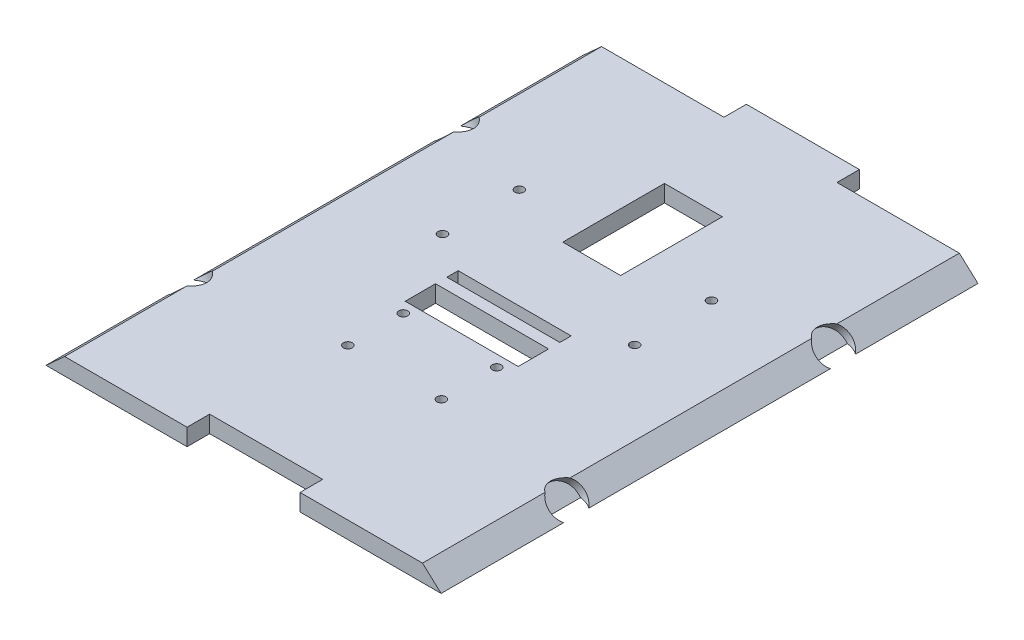
SolidWorks part; units mm, degrees
ref_plane "Front Plane" through (0, 0, 0) normal (0, 0, 1) x (1, 0, 0)
ref_plane "Top Plane" through (0, 0, 0) normal (0, 1, 0) x (1, 0, 0)
ref_plane "Right Plane" through (0, 0, 0) normal (1, 0, 0) x (0, 0, -1)
sketch "Sketch1" plane through (0, 0, 0) normal (0, 0, 1) x (1, 0, 0)
  line L0 (0, 0) -> (0, 44.45) construction
  line L1 (-40.2039, 5.9378) -> (40.2039, 5.9378)
  line L2 (-44.399, 2.1278) -> (44.399, 2.1278)
  line L3 (-40.2039, 5.9378) -> (-44.399, 2.1278)
  line L4 (40.2039, 5.9378) -> (44.399, 2.1278)
  arc A0 (44.399, 2.1278) -> (-44.399, 2.1278) centre (0, 0) ccw construction
  arc A1 (40.2039, 5.9378) -> (-40.2039, 5.9378) centre (0, 0) ccw construction
  dimension "D1" = 88.9
  dimension "D2" = 3.81
  dimension "D3" = 3.81
extrude "Boss-Extrude1" add sketch "Sketch1" along normal blind 120.65
sketch "Sketch3" plane through (0, 2.1278, 0) normal (0, -1, 0) x (1, 0, 0)
  line L0 (0, 120.65) -> (0, 0) construction
  line L1 (-44.399, 120.65) -> (44.399, 120.65) construction
  line L2 (-44.399, 0) -> (44.399, 0) construction
  line L3 (0, 60.325) -> (44.399, 60.325) construction
  line L4 (-12.7, 120.65) -> (12.7, 120.65)
  line L5 (-12.7, 120.65) -> (-12.7, 115.57)
  line L6 (-12.7, 115.57) -> (12.7, 115.57)
  line L7 (12.7, 120.65) -> (12.7, 115.57)
  line L8 (44.399, 120.65) -> (44.399, 0) construction
  line L9 (0, 60.325) -> (-44.399, 60.325) construction
  line L10 (-44.399, 120.65) -> (-44.399, 0) construction
  line L11 (12.7, -5.08) -> (12.7, 0) construction
  line L13 (-12.7, 0) -> (12.7, 0) construction
  line L14 (-12.7, -5.08) -> (-12.7, 0) construction
  line L15 (-12.7, -5.08) -> (12.7, -5.08) construction
  point P10 (12.7, 118.11)
  dimension "D1" = 25.4
  dimension "D2" = 12.7
  dimension "D3" = 5.08
extrude "Cut-Extrude1" cut sketch "Sketch3" against normal through all
sketch "Sketch4" plane through (0, 2.1278, 0) normal (0, -1, 0) x (1, 0, 0)
  line L0 (12.7, -5.0447) -> (12.7, 0.0353)
  line L1 (-12.7, 0.0353) -> (12.7, 0.0353)
  line L2 (-12.7, -5.0447) -> (-12.7, 0.0353)
  line L3 (-12.7, -5.0447) -> (12.7, -5.0447)
  line L4 (0, 115.57) -> (0, 0.0353) construction
  line L5 (-12.7, 115.57) -> (12.7, 115.57) construction
  dimension "D1" = 25.4
  dimension "D2" = 12.7
  dimension "D3" = 5.08
extrude "Boss-Extrude3" add sketch "Sketch4" against normal blind 3.81
sketch "Sketch5" plane through (0, 2.1278, 0) normal (0, -1, 0) x (-1, 0, 0)
  line L0 (0, -115.57) -> (0, 5.0447) construction
  line L1 (12.7, -115.57) -> (-12.7, -115.57) construction
  line L2 (12.7, 5.0447) -> (-12.7, 5.0447) construction
  line L3 (0, -88.6813) -> (0, -64.8053) construction
  line L4 (12.446, -88.6813) -> (-12.446, -88.6813) construction
  line L5 (12.446, -88.6813) -> (12.446, -64.8053) construction
  line L6 (12.446, -64.8053) -> (-12.446, -64.8053) construction
  line L7 (-12.446, -88.6813) -> (-12.446, -64.8053) construction
  line L8 (23.114, -55.88) -> (-23.114, -55.88) construction
  line L9 (23.114, -55.88) -> (23.114, -35.56) construction
  line L10 (23.114, -35.56) -> (-23.114, -35.56) construction
  line L11 (-23.114, -55.88) -> (-23.114, -35.56) construction
  line L12 (0, -55.88) -> (0, -35.56) construction
  line L13 (-23.114, -45.72) -> (23.114, -45.72) construction
  line L14 (12.446, -76.7433) -> (-12.446, -76.7433) construction
  line L15 (-95.9311, -70.6497) -> (-70.9311, -70.6497) construction
  line L16 (-95.9311, -70.6497) -> (-95.9311, -94.6497) construction
  line L17 (-95.9311, -94.6497) -> (-70.9311, -94.6497) construction
  line L18 (-70.9311, -70.6497) -> (-70.9311, -94.6497) construction
  line L19 (-73.5448, 8.1415) -> (-73.5448, -11.8585) construction
  line L20 (-96.4048, 8.1415) -> (-50.6848, 8.1415) construction
  line L21 (-96.4048, 8.1415) -> (-96.4048, -11.8585) construction
  line L22 (-96.4048, -11.8585) -> (-50.6848, -11.8585) construction
  line L23 (-50.6848, 8.1415) -> (-50.6848, -11.8585) construction
  line L24 (-96.4048, -1.8585) -> (-50.6848, -1.8585) construction
  line L25 (0, -19.558) -> (0, -42.418) construction
  line L26 (6.5, -19.558) -> (-6.5, -19.558)
  line L27 (6.5, -19.558) -> (6.5, -42.418)
  line L28 (6.5, -42.418) -> (-6.5, -42.418)
  line L29 (-6.5, -19.558) -> (-6.5, -42.418)
  line L30 (-12.7, 0) -> (-44.399, 0) construction
  line L31 (0, -62.2653) -> (0, -59.7253) construction
  line L32 (12.7, -62.2653) -> (-12.7, -62.2653)
  line L33 (12.7, -62.2653) -> (12.7, -59.7253)
  line L34 (12.7, -59.7253) -> (-12.7, -59.7253)
  line L35 (-12.7, -62.2653) -> (-12.7, -59.7253)
  line L36 (0, -71.6278) -> (0, -64.8053) construction
  line L37 (12.7, -71.6278) -> (-12.7, -71.6278)
  line L38 (12.7, -71.6278) -> (12.7, -64.8053)
  line L39 (12.7, -64.8053) -> (-12.7, -64.8053)
  line L40 (-12.7, -71.6278) -> (-12.7, -64.8053)
  circle A0 centre (21.59, -54.356) radius 1
  circle A1 centre (21.59, -37.084) radius 1
  circle A2 centre (-21.59, -37.084) radius 1
  circle A3 centre (-21.59, -54.356) radius 1
  circle A4 centre (-10.4422, -74.2033) radius 1
  circle A5 centre (-10.4422, -86.6493) radius 1
  circle A6 centre (10.5578, -74.2033) radius 1
  circle A7 centre (10.5578, -86.6493) radius 1
  circle A8 centre (-93.9311, -72.6497) radius 1
  circle A9 centre (-93.9311, -85.1497) radius 1
  circle A10 centre (-72.9311, -72.6497) radius 1
  circle A11 centre (-72.9311, -85.1497) radius 1
  circle A12 centre (-93.9048, 5.6415) radius 1
  circle A13 centre (-53.1848, 5.6415) radius 1
  circle A14 centre (-53.1848, -9.3585) radius 1
  circle A15 centre (-93.9048, -9.3585) radius 1
  point P53 (0, -30.988)
  dimension "D5" = 22.86
  dimension "D8" = 25.4
  dimension "D9" = 1.524
  dimension "D14" = 9.398
  dimension "D20" = 2
  dimension "D21" = 25
  dimension "D23" = 2
  dimension "D34" = 2
  dimension "D1" = 24.892
  dimension "D2" = 23.876
  dimension "D3" = 0
  dimension "D4" = 0
  dimension "D6" = 25.4
  dimension "D7" = 0
  dimension "D12" = 46.228
  dimension "D13" = 20.32
  dimension "D15" = 9.398
  dimension "D16" = 2.032
  dimension "D17" = 2.032
  dimension "D18" = 21
  dimension "D19" = 21
  dimension "D22" = 24
  dimension "D24" = 21
  dimension "D25" = 12.5
  dimension "D26" = 9.5
  dimension "D27" = 2
  dimension "D28" = 2
  dimension "D29" = 2
  dimension "D30" = 12.446
  dimension "D31" = 2.0038
  dimension "D32" = 20
  dimension "D33" = 45.72
  dimension "D35" = 2.5
  dimension "D36" = 2.5
  dimension "D37" = 13
  dimension "D38" = 6.858
  dimension "D39" = 0
  dimension "D40" = 69.85
  dimension "D41" = 35.56
  dimension "D42" = 0
  dimension "D43" = 2.54
  dimension "D44" = 2.54
  dimension "D45" = 1.524
extrude "Cut-Extrude2" cut sketch "Sketch5" against normal through all
sketch "Sketch6" plane through (-21.1272, 23.263, 0) normal (-0.6723, 0.7403, 0) x (0.7403, 0.6723, 0)
  line L0 (-28.6033, 0) -> (-28.6033, -120.65) construction
  line L1 (-25.7698, 0) -> (-31.4368, 0) construction
  line L2 (-25.7698, -60.325) -> (-32.513, -60.325) construction
  line L3 (-25.7698, -120.65) -> (-25.7698, 0) construction
  circle A0 centre (-28.6033, -30.353) radius 4
  circle A1 centre (-28.6033, -90.297) radius 4
  point P10 (-28.6033, -60.325)
  dimension "D1" = 8
  dimension "D2" = 29.972
  dimension "D3" = 120.65
extrude "Cut-Extrude3" cut sketch "Sketch6" against normal blind 2
sketch "Sketch7" plane through (21.1272, 23.263, 0) normal (0.6723, 0.7403, 0) x (0.7403, -0.6723, 0)
  line L0 (28.6033, -120.65) -> (28.6033, 0) construction
  line L1 (31.4368, -120.65) -> (25.7698, -120.65) construction
  line L2 (25.7698, -60.325) -> (31.6985, -60.325) construction
  line L3 (25.7698, -120.65) -> (25.7698, 0) construction
  circle A0 centre (28.6033, -90.297) radius 4
  circle A1 centre (28.6033, -30.353) radius 4
  point P11 (28.6033, -60.325)
  dimension "D1" = 8
  dimension "D2" = 29.972
  dimension "D3" = 120.65
extrude "Cut-Extrude4" cut sketch "Sketch7" against normal blind 2
